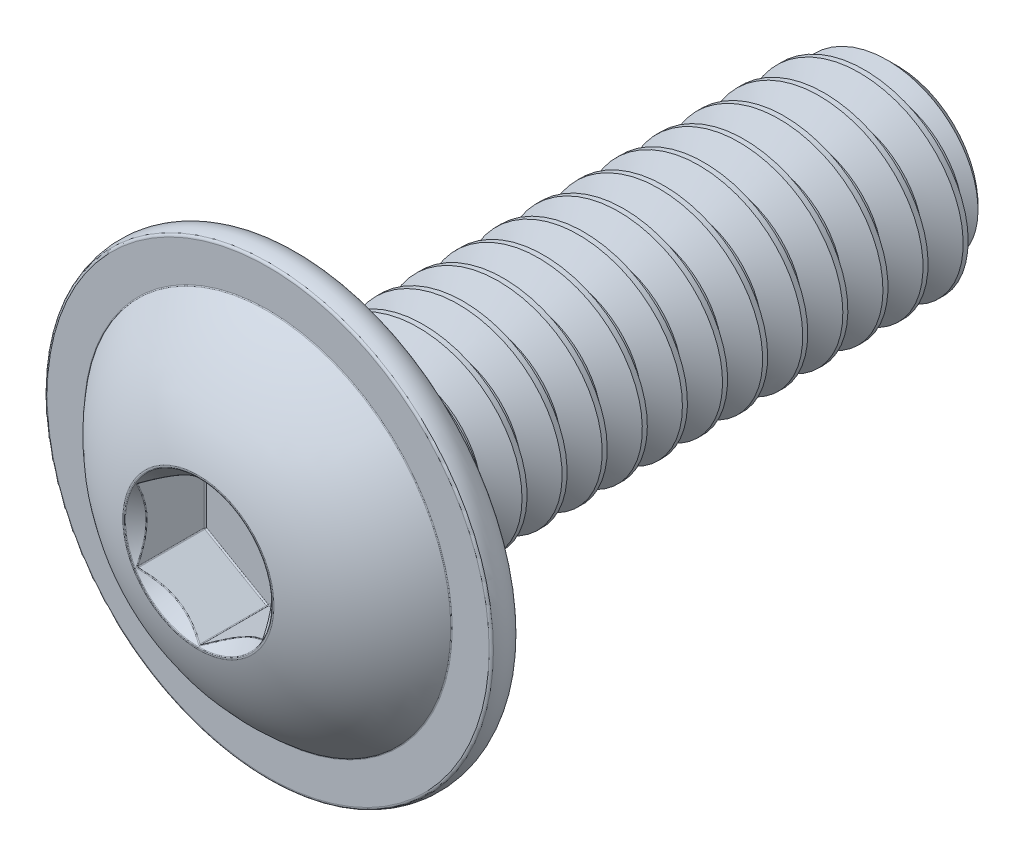
SolidWorks part; units mm, degrees
ref_plane "Front Plane" through (0, 0, 0) normal (0, 0, 1) x (1, 0, 0)
ref_plane "Top Plane" through (0, 0, 0) normal (0, 1, 0) x (1, 0, 0)
ref_plane "Right Plane" through (0, 0, 0) normal (1, 0, 0) x (0, 0, -1)
sketch "Sketch1" plane through (0, 0, 0) normal (1, 0, 0) x (0, 0, -1)
  line L0 (-11.0744, 0) -> (11.0744, 0) construction
  line L1 (11.0744, 0) -> (11.0744, 3.175)
  line L2 (11.0744, 3.175) -> (-7.9756, 3.175)
  line L3 (-7.9756, 3.175) -> (-7.9756, 0)
  line L4 (11.0744, 0) -> (12.3444, 0) construction
  line L5 (11.0744, 2.54) -> (10.4394, 3.175)
  line L6 (-7.9756, 3.175) -> (-7.9756, 7.1437)
  line L7 (-7.9756, 7.1437) -> (-8.8646, 7.1437)
  line L8 (-8.8646, 7.1437) -> (-8.8646, 6.2547)
  line L9 (-11.0744, 0) -> (-11.0744, 2.2914)
  line L10 (-8.8646, 6.2547) -> (-8.8646, 5.3657) construction
  line L11 (-11.0744, 2.2914) -> (-13.0588, 1.1457)
  line L12 (-13.0588, 1.1457) -> (-13.0588, -1.1457)
  line L13 (-13.0588, -1.1457) -> (-11.0744, -2.2914)
  line L14 (-11.0744, -2.2914) -> (-9.09, -1.1457)
  line L15 (-9.09, -1.1457) -> (-9.09, 1.1457)
  line L16 (-9.09, 1.1457) -> (-11.0744, 2.2914)
  line L17 (-7.9756, 3.683) -> (-7.9756, -3.683) construction
  circle A1 centre (-11.0744, 0) radius 1.9844 construction
  arc A3 (-8.8646, 5.8102) -> (-11.0744, 2.3906) centre (-4.9402, 0.8505) ccw
  point P2 (0, 0)
  point P10 (9.1694, -3.175)
  point P16 (11.0744, -3.175)
  point P17 (-7.9756, 7.1437)
  point P18 (11.0744, 3.175)
  point P20 (9.1694, 3.175)
  dimension "Head Radii" = 6.3246
  dimension "D1" = 45
  dimension "D3" = 0.635
  dimension "D4" = 1.905
  dimension "D2" = 0.0992
sketch "Sketch3" plane through (0, 0, 0) normal (1, 0, 0) x (0, 0, -1)
  line L0 (-7.9756, 3.175) -> (-7.9756, 7.1437) construction
  line L1 (-7.9756, 7.1437) -> (-8.8646, 7.1437) construction
  line L2 (-7.9756, 7.1437) -> (-7.9756, 3.683) construction
  line L3 (-11.0744, 0) -> (-11.0744, 2.2914) construction
  line L4 (-7.9756, 3.175) -> (-7.9756, 7.1437) construction
  line L5 (-7.9756, 7.1437) -> (-8.8646, 7.1437) construction
  line L7 (-11.0744, 0) -> (-11.0744, 2.3906)
  line L8 (-7.9756, 3.175) -> (10.4394, 3.175) construction
  line L9 (10.4394, 3.175) -> (11.0744, 2.54)
  line L10 (11.0744, 2.54) -> (11.0744, 0)
  line L11 (11.0744, 0) -> (-11.0744, 0)
  line L12 (-8.8646, 5.8102) -> (-8.8646, 7.1437) construction
  line L13 (-7.4676, 3.175) -> (10.4394, 3.175)
  line L14 (-8.8646, 5.8102) -> (-8.8646, 7.0548)
  line L15 (-7.9756, 3.683) -> (-7.9756, 6.9659)
  line L16 (-8.8646, 7.1437) -> (-8.8646, 6.9659) construction
  arc A0 (-8.8646, 5.8102) -> (-11.0744, 2.3906) centre (-4.9402, 0.8505) ccw construction
  arc A2 (-8.8646, 7.0548) -> (-7.9756, 6.9659) centre (-8.4901, 6.3105) cw
  arc A4 (-8.8646, 5.8102) -> (-11.0744, 2.3906) centre (-4.9402, 0.8505) ccw
  arc A5 (-7.9756, 3.683) -> (-7.4676, 3.175) centre (-7.4676, 3.683) ccw
  dimension "D1" = 0.1778
revolve "Revolve1" add sketch "Sketch3" angle 360 about L11
sketch "Sketch4" plane through (0, 0, 11.0744) normal (0, 0, 1) x (1, 0, 0)
  line L13 (0, 2.2914) -> (-1.9844, 1.1457)
  line L14 (-1.9844, 1.1457) -> (-1.9844, -1.1457)
  line L15 (-1.9844, -1.1457) -> (0, -2.2914)
  line L16 (0, -2.2914) -> (1.9844, -1.1457)
  line L17 (1.9844, -1.1457) -> (1.9844, 1.1457)
  line L18 (1.9844, 1.1457) -> (0, 2.2914)
  circle A0 centre (0, 0) radius 1.9844 construction
  dimension "D1" = 3.9688
extrude "Cut-Extrude1" cut sketch "Sketch4" against normal up to surface (2.2098 mm away) up to face at (-5.8102, 0, 8.8646)
sketch "Sketch5" plane through (0, 0, 11.0744) normal (0, 0, 1) x (1, 0, 0)
  line L0 (0, 2.2914) -> (0, 2.331) construction
  circle A1 centre (0, 0) radius 2.331
  dimension "D1" = 0.0397
extrude "Cut-Extrude2" cut sketch "Sketch5" against normal up to surface (2.2098 mm away) draft 45 up to face at (0, 0, 8.8646)
fillet "Fillet3" radius 0.0397 21 edges at (-1.1168, -1.6466, 10.7329) (0.8676, -1.7905, 10.7329) (0, -2.2914, 9.9497) (1.9844, -0.0244, 10.7279) (1.9844, -1.1457, 9.9497) (1.1168, 1.6466, 10.7329) (1.9844, 1.1457, 9.9497) (1.9844, 0, 8.8646) (0.9922, -1.7185, 8.8646) (-0.9922, -1.7185, 8.8646) (0.9922, 1.7185, 8.8646) (-1.9844, 0, 8.8646) (-1.9844, -1.1457, 9.9497) (-1.9844, -0.0244, 10.7279) (-0.9922, 1.7185, 8.8646) (-1.9844, 1.1457, 9.9497) (-0.8676, 1.7905, 10.7329) (0, 2.2914, 9.9497) (-2.3906, 0, 11.0744) (2.331, 0, 11.0744) (-5.8102, 0, 8.8646)
fillet "Fillet4" radius 0.0889 2 edges at (-6.9659, 0, 7.9756) (-7.0549, 0, 8.8646)
sketch "Reference Sketch1" plane through (0, 0, 0) normal (0, 0, 1) x (1, 0, 0)
  circle A0 centre (0, 0) radius 7.1437 construction
ref_plane "Plane1" through (0, 0, 7.4676) normal (0, 0, 1) x (1, 0, 0)
split "Split1" trim tools "Plane1" bodies to split 106 resulting bodies 108 111
sketch "Sketch6" plane through (0, 0, -11.0744) normal (0, 0, -1) x (-1, 0, 0)
  circle A1 centre (0, 0) radius 3.175
curve "Helix/Spiral1" pitch 1.27 height 20.955 radius 3.175 centre (0, 0, -11.0744) axis (0, 0, 1) start towards (0, 1, 0)
sketch "Sketch7" plane through (0, 0, 0) normal (1, 0, 0) x (0, 0, -1)
  line L0 (10.995, 3.3125) -> (11.63, 2.2126) construction
  line L1 (11.63, 2.2126) -> (12.265, 3.3125) construction
  line L2 (12.265, 3.3125) -> (10.995, 3.3125) construction
  line L3 (11.0347, 3.2437) -> (12.2253, 3.2437)
  line L4 (12.2253, 3.2437) -> (11.7094, 2.3501)
  line L5 (11.7094, 2.3501) -> (11.5507, 2.3501)
  line L6 (11.5507, 2.3501) -> (11.0347, 3.2437)
  line L7 (11.63, 2.3501) -> (11.63, 2.2126) construction
  line L8 (11.0744, 3.175) -> (12.1857, 3.175) construction
  line L9 (11.63, 3.3125) -> (11.63, 3.175) construction
  point P12 (11.63, 3.2437)
  dimension "D1" = 1.27
  dimension "D2" = 0.1588
sweep "Cut-Sweep1" cut profiles "Sketch7" path "Helix/Spiral1" align with end faces yes
sketch "Sketch8" plane through (0, 0, 7.4676) normal (0, 0, 1) x (1, 0, 0)
  circle A2 centre (0, 0) radius 3.175
  circle A3 centre (0, 0) radius 3.175
  dimension "D1" = 0
extrude "Boss-Extrude1" add sketch "Sketch8" against normal through all draft 45
equation "\"D3@Sketch1\"=0.5*\"Pitch@Sketch1\""
equation "\"D4@Helix/Spiral1\"=\"Pitch@Sketch1\""
equation "\"D3@Helix/Spiral1\"=\"Pitch@Sketch1\"*1.5+\"Length@Sketch1\""
equation "\"D1@Sketch7\"=\"Pitch@Sketch1\""
equation "\"D2@Sketch7\"=\"D1@Sketch7\"/8"
equation "\"D4@Sketch1\"=\"Pitch@Sketch1\"*1.5"
equation "\"D1@Sketch4\"=\"Drive Size@Sketch1\""
equation "\"D1@Sketch5\"=\"Drive Size@Sketch1\"*0.01"
equation "\"D2@Sketch1\"=\"Drive Size@Sketch1\"*0.025"
equation "\"D1@Fillet3\"=\"Drive Size@Sketch1\"*0.01"
equation "\"D1@Fillet4\"=(\"Head Height@Sketch1\"-\"Hex Key Engagement@Sketch1\")*0.1"
equation "\"D1@Sketch3\"=(\"Head Height@Sketch1\"-\"Hex Key Engagement@Sketch1\")*0.2"
